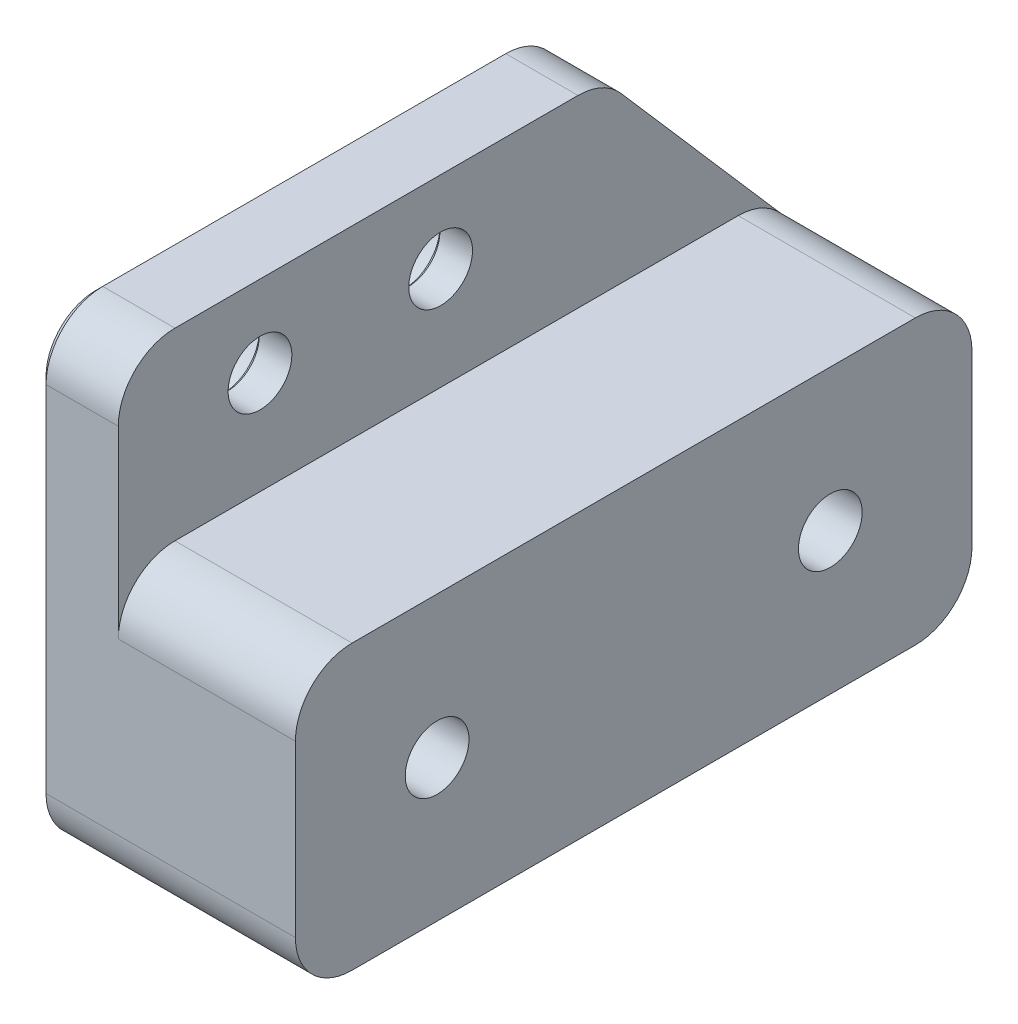
SolidWorks part; units mm, degrees
ref_plane "Front Plane" through (0, 0, 0) normal (0, 0, 1) x (1, 0, 0)
ref_plane "Top Plane" through (0, 0, 0) normal (0, 1, 0) x (1, 0, 0)
ref_plane "Right Plane" through (0, 0, 0) normal (1, 0, 0) x (0, 0, -1)
sketch "Sketch1" plane through (0, 0, 0) normal (1, 0, 0) x (0, 0, -1)
  line L0 (0, -10) -> (0, 23) construction
  line L1 (37.75, 0) -> (-10, 0) construction
  line L2 (-6, -10) -> (33.75, -10)
  line L3 (37.75, -6) -> (37.75, 6)
  line L4 (22.4457, 23) -> (-6, 23)
  line L6 (-10, 19) -> (-10, -6)
  line L7 (12.75, 17.25) -> (27.75, 0) construction
  line L8 (0, 17.25) -> (12.75, 17.25) construction
  line L9 (25.4641, 21.6247) -> (36.7684, 8.6247)
  circle A0 centre (0, 0) radius 2 construction
  circle A1 centre (0, 17.25) radius 2 construction
  circle A2 centre (27.75, 0) radius 2.25
  circle A3 centre (0, 17.25) radius 2.25
  circle A4 centre (0, 0) radius 2.25
  arc A5 (33.75, -10) -> (37.75, -6) centre (33.75, -6) ccw
  arc A7 (-6, 23) -> (-10, 19) centre (-6, 19) ccw
  arc A9 (-10, -6) -> (-6, -10) centre (-6, -6) ccw
  circle A10 centre (12.75, 17.25) radius 2.25
  arc A11 (22.4457, 23) -> (25.4641, 21.6247) centre (22.4457, 19) cw
  arc A12 (36.7684, 8.6247) -> (37.75, 6) centre (33.75, 6) cw
  point P25 (0, 0)
  point P26 (24.753, 21.6247)
  point P32 (0, 0)
  point P35 (37.75, 0)
  dimension "D2" = 4
  dimension "D3" = 4
  dimension "D8" = 4
  dimension "D6" = 17.25
  dimension "D9" = 5.75
  dimension "D11" = 10
  dimension "D5" = 10
  dimension "D7" = 12.75
  dimension "D10" = 10
  dimension "D12" = 15
  dimension "D1" = 0.25
  dimension "D4" = 0.25
extrude "Boss-Extrude1" add sketch "Sketch1" along normal blind 2.6
sketch "Sketch3" plane through (0, 0, 0) normal (1, 0, 0) x (0, 0, -1)
  line L5 (-6, -10) -> (33.75, -10)
  line L6 (37.75, -6) -> (37.75, 6)
  line L7 (22.4457, 23) -> (-6, 23)
  line L8 (36.7684, 8.6247) -> (25.4641, 21.6247)
  line L9 (-10, 19) -> (-10, -6)
  line L10 (-6, -10) -> (33.75, -10)
  line L11 (37.75, -6) -> (37.75, 6)
  line L12 (22.4457, 23) -> (-6, 23)
  line L14 (-10, 19) -> (-10, -6)
  line L20 (36.7684, 8.6247) -> (25.4641, 21.6247)
  circle A0 centre (0, 0) radius 3.5 construction
  circle A1 centre (27.75, 0) radius 3.75
  circle A2 centre (27.75, 0) radius 2.25 construction
  circle A3 centre (0, 0) radius 2.25 construction
  circle A4 centre (0, 0) radius 3.75
  arc A5 (-10, -6) -> (-6, -10) centre (-6, -6) ccw
  arc A6 (33.75, -10) -> (37.75, -6) centre (33.75, -6) ccw
  arc A7 (37.75, 6) -> (36.7684, 8.6247) centre (33.75, 6) ccw
  arc A8 (-6, 23) -> (-10, 19) centre (-6, 19) ccw
  arc A9 (37.75, 6) -> (36.7684, 8.6247) centre (33.75, 6) ccw
  arc A10 (-10, -6) -> (-6, -10) centre (-6, -6) ccw
  arc A11 (33.75, -10) -> (37.75, -6) centre (33.75, -6) ccw
  arc A13 (-6, 23) -> (-10, 19) centre (-6, 19) ccw
  circle A15 centre (0, 17.25) radius 3.75
  circle A16 centre (0, 17.25) radius 2.25 construction
  circle A18 centre (12.75, 17.25) radius 3.75
  circle A19 centre (12.75, 17.25) radius 2.25 construction
  arc A22 (25.4641, 21.6247) -> (22.4457, 23) centre (22.4457, 19) ccw
  arc A23 (25.4641, 21.6247) -> (22.4457, 23) centre (22.4457, 19) ccw
  dimension "D2" = 7
  dimension "D3" = 0.25
extrude "Boss-Extrude3" add sketch "Sketch3" against normal blind 3
chamfer "Chamfer2" distance 0.3 angle 45 8 edges at (0, 0, -31.5) (0, 0, -30) (0, 0, -3.75) (0, 0, -2.25) (0, 17.25, -2.25) (0, 17.25, -3.75) (0, 17.25, -16.5) (0, 17.25, -15)
chamfer "Chamfer3" distance 0.5 angle 45 14 edges at (-3, 0, -3.75) (-3, 6.5, 10) (-3, 21.8284, 8.8284) (-3, 23, -8.2228) (-3, 0, -37.75) (-3, -8.8284, -36.5784) (-3, -10, -13.875) (-3, -8.8284, 8.8284) (-3, 0, -31.5) (-3, 17.25, -3.75) (-3, 7.4011, -37.4966) (-3, 15.1247, -31.1162) (-3, 22.64, -24.1041) (-3, 17.25, -16.5)
sketch "Sketch4" plane through (2.6, 0, 0) normal (1, 0, 0) x (0, 0, -1)
  line L0 (-6, -10) -> (33.75, -10) construction
  line L1 (-6, -10) -> (33.75, -10)
  line L2 (-25, 0) -> (10, 0) construction
  line L6 (37.75, -6) -> (37.75, 6)
  line L7 (-6, 10) -> (33.75, 10)
  line L8 (37.75, -6) -> (37.75, 6) construction
  line L9 (-10, -6) -> (-10, 6)
  line L10 (-10, 19) -> (-10, -6) construction
  circle A0 centre (0, 0) radius 2.25 construction
  circle A1 centre (27.75, 0) radius 2.25 construction
  arc A2 (33.75, -10) -> (37.75, -6) centre (33.75, -6) ccw construction
  arc A3 (-10, -6) -> (-6, -10) centre (-6, -6) ccw construction
  circle A4 centre (0, 0) radius 2.25
  circle A5 centre (27.75, 0) radius 2.25
  arc A6 (33.75, -10) -> (37.75, -6) centre (33.75, -6) ccw
  arc A7 (-10, -6) -> (-6, -10) centre (-6, -6) ccw
  arc A8 (-10, 6) -> (-6, 10) centre (-6, 6) cw
  arc A9 (37.75, 6) -> (33.75, 10) centre (33.75, 6) ccw
  arc A10 (37.75, 6) -> (36.7684, 8.6247) centre (33.75, 6) ccw construction
  point P16 (0, 0)
  point P17 (0, 0)
  point P19 (37.75, 6)
  dimension "D1" = 20
extrude "Boss-Extrude4" add sketch "Sketch4" along normal blind 12.5
equation "\"Tolerance\" = 0.25mm"
equation "\"D1@Sketch1\"=\"Tolerance\""
equation "\"D4@Sketch1\"=\"Tolerance\""
equation "\"Pocket_Head_M5\"= 8mm"
equation "\"Pocket_Head_M4\" = 7mm"
equation "\"D2@Sketch3\"=\"Pocket_Head_M4\""
equation "\"D3@Sketch3\"=\"Tolerance\""
equation "\"Pocket_Nut_M4\" = 7mm"
